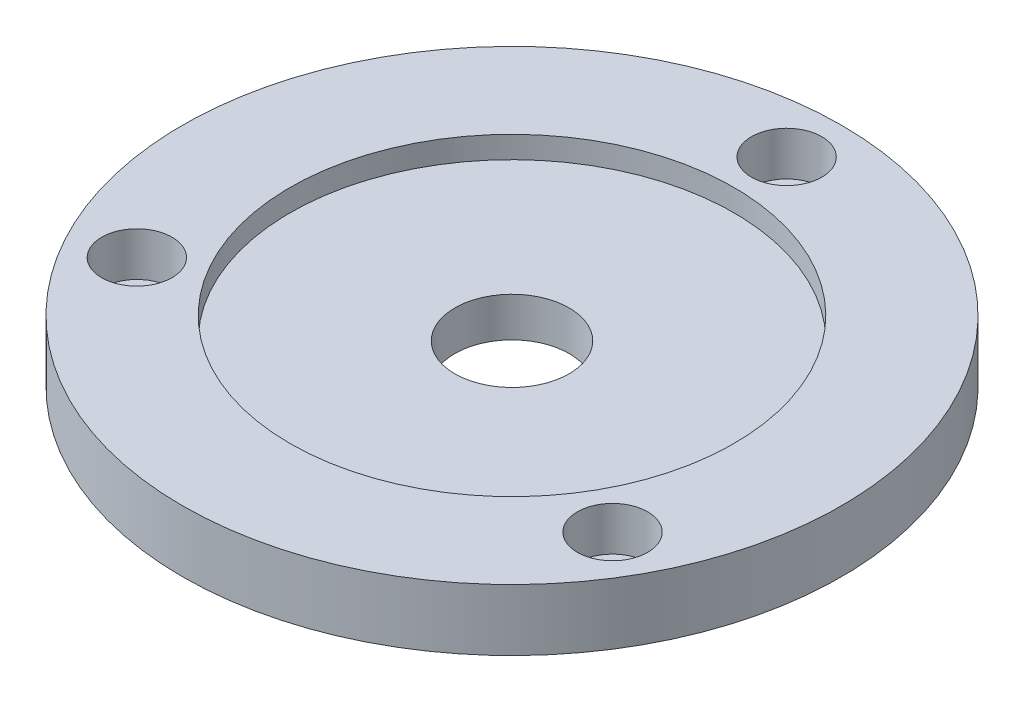
SolidWorks part; units mm, degrees
ref_plane "Front Plane" through (0, 0, 0) normal (0, 0, 1) x (1, 0, 0)
ref_plane "Top Plane" through (0, 0, 0) normal (0, 1, 0) x (1, 0, 0)
ref_plane "Right Plane" through (0, 0, 0) normal (1, 0, 0) x (0, 0, -1)
sketch "Sketch1" plane through (0, 0, 0) normal (0, 1, 0) x (1, 0, 0)
  circle A0 centre (0, 0) radius 75
  dimension "D1" = 150
extrude "Boss-Extrude1" add sketch "Sketch1" along normal blind 14
sketch "Sketch2" plane through (0, 14, 0) normal (0, 1, 0) x (1, 0, 0)
  circle A0 centre (0, 0) radius 13
  dimension "D1" = 26
sketch "Sketch4" plane through (0, 14, 0) normal (0, 1, 0) x (1, 0, 0)
  line L0 (0, 0) -> (0, 62.5) construction
  line L1 (0, 0) -> (54.1266, -31.25) construction
  line L2 (0, 0) -> (-54.1266, -31.25) construction
  circle A0 centre (0, 62.5) radius 5
  circle A1 centre (-54.1266, -31.25) radius 5
  circle A2 centre (54.1266, -31.25) radius 5
  circle A3 centre (0, 0) radius 62.5
  dimension "D1" = 10
  dimension "D2" = 10
  dimension "D3" = 10
  dimension "D4" = 62.5
  dimension "D5" = 120
extrude "Cut-Extrude4" cut sketch "Sketch4" against normal through all contours A3 A0 | A0 A3 | A2 A3 | A3 A2 | A3 A1 | A1 A3 region at (0, 14, -64.5856) region at (0, 14, -60.3423) region at (-55.9328, 14, 32.2928) region at (-52.258, 14, 30.1712) region at (52.258, 14, 30.1712) region at (55.9328, 14, 32.2928)
extrude "Cut-Extrude5" cut sketch "Sketch2" against normal through all
sketch "Sketch5" plane through (0, 14, 0) normal (0, 1, 0) x (-1, 0, 0)
  circle A0 centre (0, 0) radius 50.5
  dimension "D1" = 101
extrude "Cut-Extrude6" cut sketch "Sketch5" against normal blind 5
sketch "Sketch6" plane through (0, 14, 0) normal (0, 1, 0) x (1, 0, 0)
  circle A0 centre (-54.1266, -31.25) radius 8
  circle A1 centre (0, 62.5) radius 8
  circle A2 centre (54.1266, -31.25) radius 8
  dimension "D1" = 16
  dimension "D2" = 16
  dimension "D3" = 16
extrude "Cut-Extrude7" cut sketch "Sketch6" against normal blind 10
